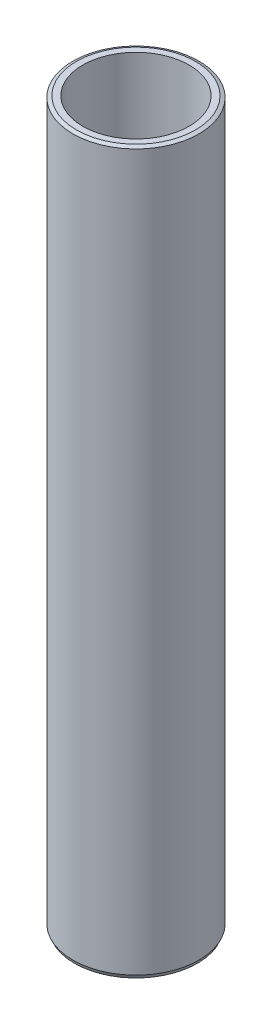
SolidWorks part; units mm, degrees
ref_plane "Front Plane" through (0, 0, 0) normal (0, 0, 1) x (1, 0, 0)
ref_plane "Top Plane" through (0, 0, 0) normal (0, 1, 0) x (1, 0, 0)
ref_plane "Right Plane" through (0, 0, 0) normal (1, 0, 0) x (0, 0, -1)
sketch "Sketch1" plane through (0, 0, 0) normal (0, 1, 0) x (1, 0, 0)
  circle A0 centre (0, 0) radius 52.5
  dimension "SHAFT_OD" = 105
extrude "Boss-Extrude1" add sketch "Sketch1" along normal blind 600
sketch "Sketch2" plane through (0, 0, 0) normal (0, 1, 0) x (1, 0, 0)
  circle A0 centre (0, 0) radius 44.2414
  dimension "BORE_D" = 88.4828
extrude "Cut-Extrude1" cut sketch "Sketch2" along normal through all
chamfer "Chamfer1" distance 1.3253 angle 66.114 2 edges at (0, 600, 52.5) (0, 0, 52.5) first distance on face at (0, 600, 52.5) first distance on face at (0, 0, 44.2414)
